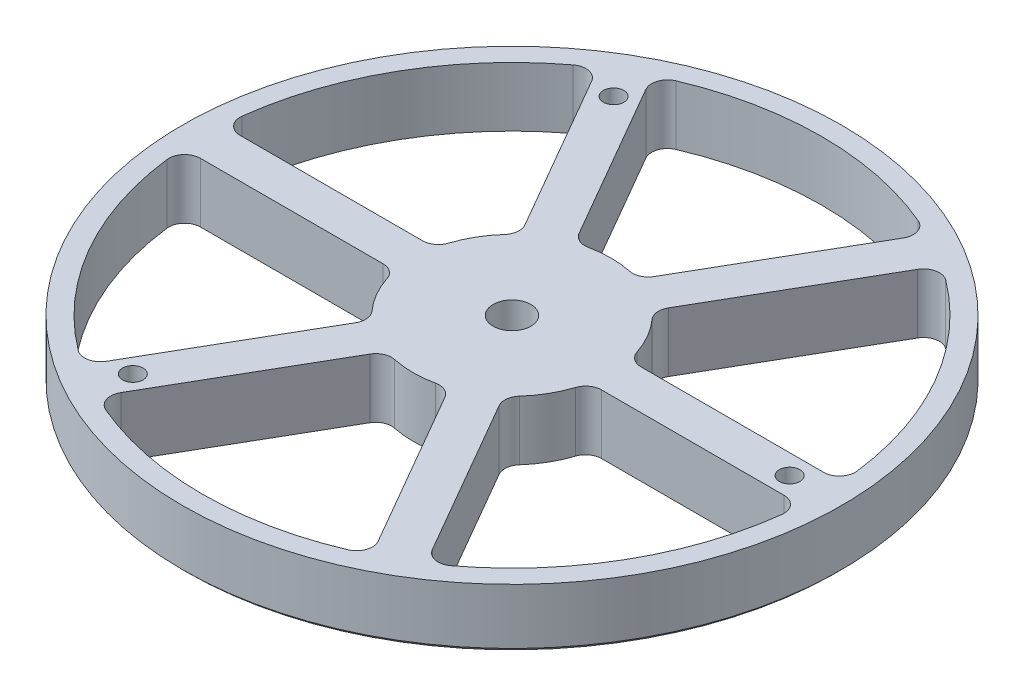
SolidWorks part; units mm, degrees
ref_plane "Front Plane" through (0, 0, 0) normal (0, 0, 1) x (1, 0, 0)
ref_plane "Top Plane" through (0, 0, 0) normal (0, 1, 0) x (1, 0, 0)
ref_plane "Right Plane" through (0, 0, 0) normal (1, 0, 0) x (0, 0, -1)
sketch "Sketch2" plane through (0, 0, 0) normal (1, 0, 0) x (0, 0, -1)
  line L0 (0, 0) -> (-83.0999, 0)
  line L1 (-83.0999, 0) -> (-83.0999, 15)
  line L2 (-83.0999, 15) -> (0, 15)
  line L5 (0, 15) -> (0, 0)
  dimension "D1" = 83.0999
  dimension "D2" = 15
ref_axis "Axis1" through (0, -0.75, 0) along (0, 1, 0)
revolve "Revolve1" add sketch "Sketch2" angle 360 about axis through (0, -0.75, 0) along (0, 1, 0)
hole_wizard "#6 (0.204) Diameter Hole1" positions "Sketch6" profile "Sketch7" hole size "#6" standard "ANSI Inch" end condition through all
sketch "Sketch6" plane through (0, 15, 0) normal (0, 1, 0) x (1, 0, 0)
  line L0 (0, 0) -> (-69.8201, 120.932) construction
  line L2 (0, 0) -> (0, 109.0908) construction
  point P0 (-35, 60.6218)
  dimension "D1" = 30
  dimension "D2" = 70
sketch "Sketch7" plane through (-35, 15, -60.6218) normal (1, 0, 0) x (0, 0, 1)
  line L0 (0, 0) -> (0, 15)
  line L1 (0, 15) -> (2.5908, 15)
  line L2 (2.5908, 15) -> (2.5908, 0)
  line L5 (2.5908, 0) -> (0, 0)
  line L11 (0, -6.35) -> (0, 107.95) construction
  dimension "Thru Hole Dia." = 5.1816
  dimension "Thru Hole Depth" = 15
pattern_circular "CirPattern3" count 3 over 360 about axis through (0, -0.75, 0) along (0, 1, 0) of "#6 (0.204) Diameter Hole1"
sketch "Sketch8" plane through (0, 15, 0) normal (0, 1, 0) x (1, 0, 0)
  line L4 (0, 0) -> (0, 93.9995) construction
  line L5 (0, 0) -> (113.8372, 0) construction
  line L6 (-7.9173, 23.7132) -> (-34.6397, 69.9978)
  line L7 (7.9173, 23.7132) -> (34.6397, 69.9978)
  line L8 (0, 0) -> (-35, 60.6218) construction
  arc A0 (-7.9173, 23.7132) -> (7.9173, 23.7132) centre (0, 0) cw
  arc A1 (-34.6397, 69.9978) -> (34.6397, 69.9978) centre (0, 0) cw
  circle A2 centre (0, 0) radius 83.0999 construction
  dimension "D1" = 25
  dimension "D2" = 5
  dimension "D3" = 5
extrude "Cut-Extrude1" cut sketch "Sketch8" against normal through all
fillet "Fillet1" radius 4 4 edges at (7.9173, 7.5, -23.7132) (34.6397, 7.5, -69.9978) (-7.9173, 7.5, -23.7132) (-34.6397, 7.5, -69.9978)
pattern_circular "CirPattern4" count 6 over 360 about axis through (0, -0.75, 0) along (0, 1, 0) of "Cut-Extrude1", "Fillet1"
chamfer "Chamfer2" distance 1 angle 45 1 edges at (0, 0, -83.0999)
hole_wizard "3/8 (0.375) Diameter Hole1" positions "Sketch9" profile "Sketch11" hole size "3/8" standard "ANSI Inch" end condition through all
sketch "Sketch9" plane through (0, 0, 0) normal (0, -1, 0) x (-1, 0, 0)
  point P0 (0, 0)
sketch "Sketch11" plane through (0, 0, 0) normal (1, 0, 0) x (0, 0, -1)
  line L0 (0, 0) -> (0, 15)
  line L1 (0, 15) -> (4.7625, 15)
  line L2 (4.7625, 15) -> (4.7625, 0)
  line L5 (4.7625, 0) -> (0, 0)
  line L11 (0, -6.35) -> (0, 107.95) construction
  dimension "Thru Hole Dia." = 9.525
  dimension "Thru Hole Depth" = 15
equation "\"TubeDiameter\" = 6.5433in"
equation "\"D1@Sketch2\"=\"TubeDiameter\"/2"
